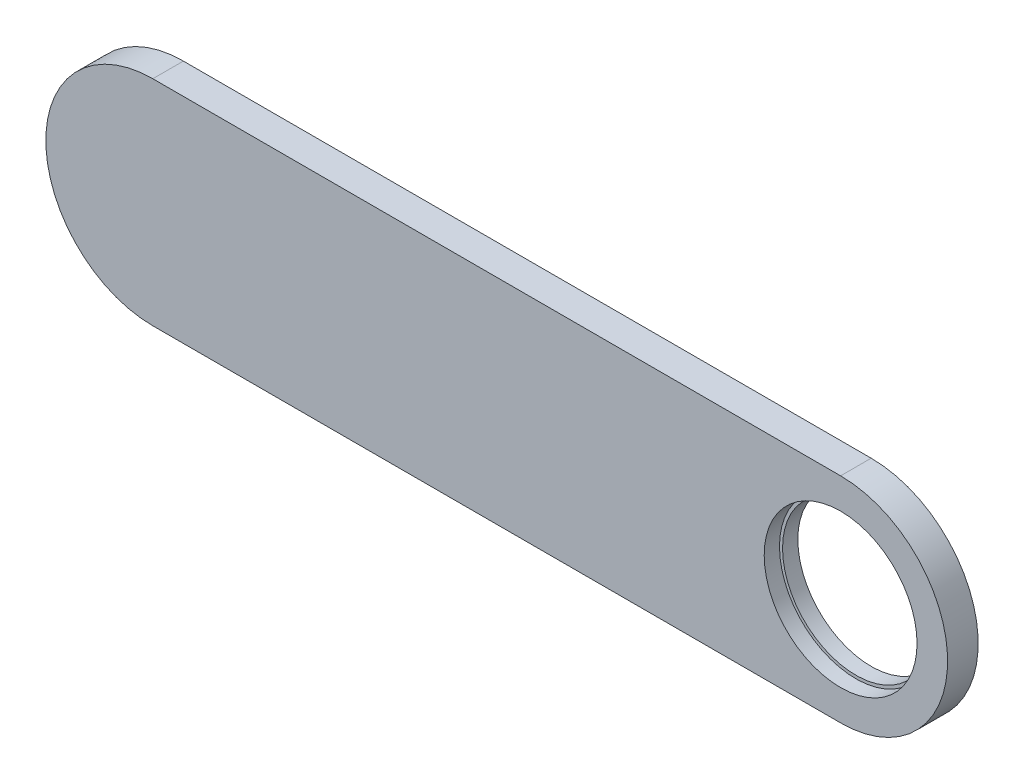
SolidWorks part; units mm, degrees
material "PVC rigide"
ref_plane "Plan de face" through (0, 0, 0) normal (0, 0, 1) x (1, 0, 0)
ref_plane "Plan de dessus" through (0, 0, 0) normal (0, 1, 0) x (1, 0, 0)
ref_plane "Plan de droite" through (0, 0, 0) normal (1, 0, 0) x (0, 0, -1)
sketch "Esquisse1" plane through (0, 0, 0) normal (0, 0, 1) x (1, 0, 0)
  line L0 (0, 0) -> (-450, 0) construction
  line L1 (0, -70) -> (-450, -70)
  line L2 (0, 70) -> (-450, 70)
  circle A0 centre (0, 0) radius 50
  arc A1 (0, -70) -> (0, 70) centre (0, 0) ccw
  arc A2 (-450, 70) -> (-450, -70) centre (-450, 0) ccw
  point P4 (-225, 0)
  dimension "D1" = 100
  dimension "D3" = 20
  dimension "D2" = 450
extrude "Boss.-Extru.1" add sketch "Esquisse1" along normal blind 20
sketch "Esquisse2" plane through (0, 0, 0) normal (0, 0, -1) x (-1, 0, 0)
  circle A2 centre (0, 0) radius 48
  circle A3 centre (0, 0) radius 50 construction
  circle A4 centre (0, 0) radius 50
  dimension "D1" = 2
extrude "Boss.-Extru.2" add sketch "Esquisse2" against normal blind 10
